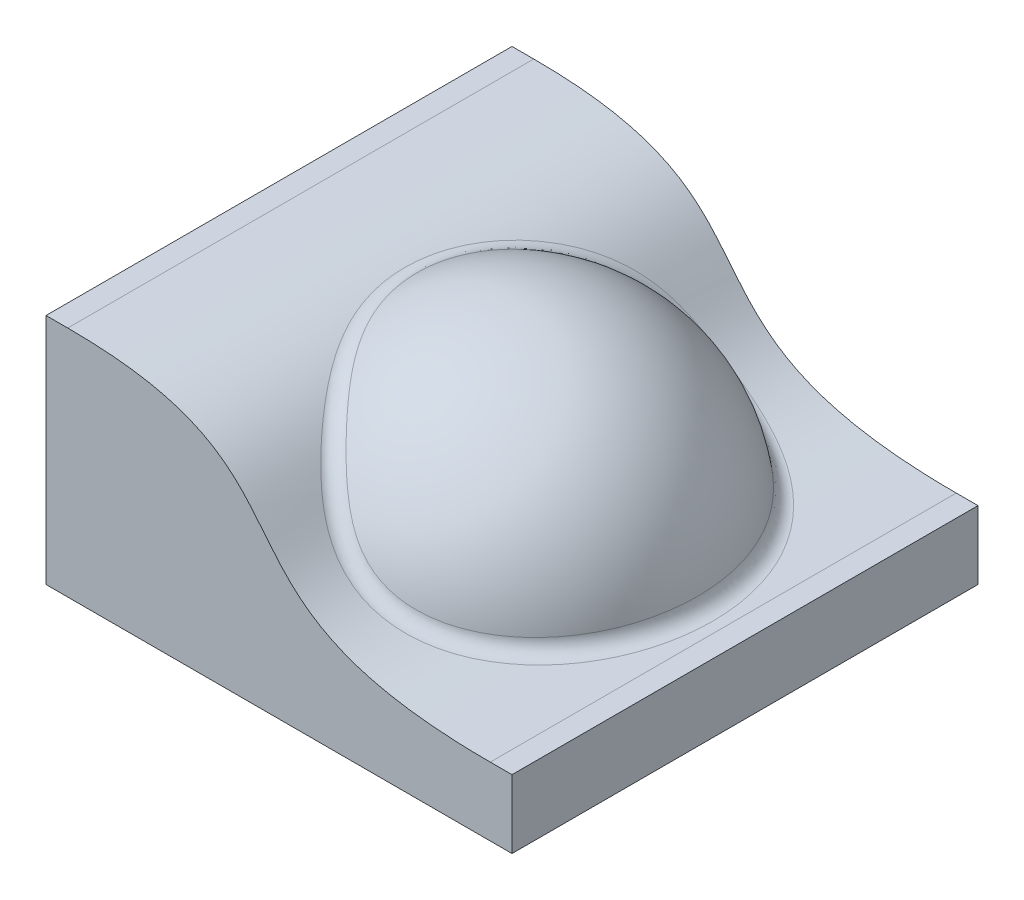
SolidWorks part; units mm, degrees
material "1345 Alloy"
ref_plane "Front Plane" through (0, 0, 0) normal (0, 0, 1) x (1, 0, 0)
ref_plane "Top Plane" through (0, 0, 0) normal (0, 1, 0) x (1, 0, 0)
ref_plane "Right Plane" through (0, 0, 0) normal (1, 0, 0) x (0, 0, -1)
sketch "Sketch1" plane through (0, 0, 0) normal (0, 0, 1) x (1, 0, 0)
  line L0 (68, -58) -> (75, -58)
  line L1 (75, -58) -> (75, -80)
  line L2 (-75, -5) -> (-75, -80)
  line L3 (-75, -80) -> (75, -80)
  line L5 (-75, -5) -> (-68, -5)
  spline S2 degree 3 poles (-68, -5) (19.7194, -5) (-30.3251, -58) (68, -58) knots 0 0 0 0 1 1 1 1
  point P3 (0, -80)
  dimension "D1" = 150
  dimension "D2" = 75
  dimension "D3" = 7
  dimension "D4" = 22
  dimension "D5" = 5
extrude "Extrude1" add sketch "Sketch1" against normal blind 75 and the other way blind 75
ref_axis "Axis1" through (0, 11.1852, 0) along (0, -1, 0)
sketch "Sketch2" plane through (0, 0, 0) normal (0, 0, 1) x (1, 0, 0)
  line L0 (0, 11.1852) -> (0, -79.1041) construction
  line L1 (0, -60) -> (60, -60)
  line L2 (0, -60) -> (0, 0)
  arc A0 (60, -60) -> (0, 0) centre (0, -60) ccw
  dimension "D1" = 60
revolve "Revolve1" add sketch "Sketch2" angle 360 about axis through (0, 11.1852, 0) along (0, -1, 0)
fillet "Fillet2" radius 5 1 edges at (-31.0838, -9.9678, -11.4269)
